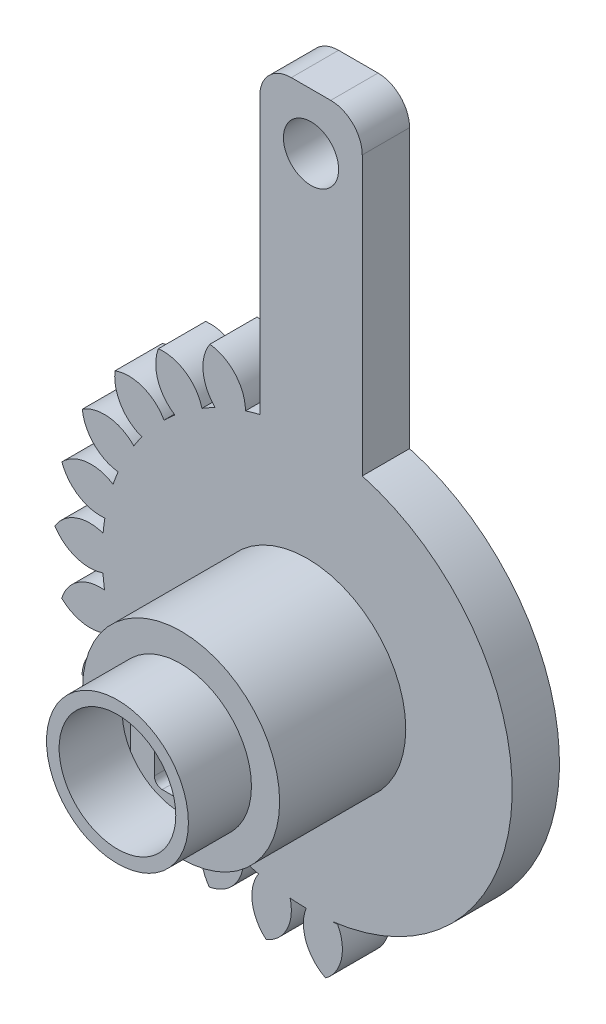
SolidWorks part; units mm, degrees
ref_plane "Front Plane" through (0, 0, 0) normal (0, 0, 1) x (1, 0, 0)
ref_plane "Top Plane" through (0, 0, 0) normal (0, 1, 0) x (1, 0, 0)
ref_plane "Right Plane" through (0, 0, 0) normal (1, 0, 0) x (0, 0, -1)
ref_plane "Plane1" through (0, 0, 5) normal (0, 0, 1) x (1, 0, 0)
ref_plane "Plane2" through (0, 0, 8) normal (0, 0, 1) x (1, 0, 0)
ref_plane "Plane3" through (0, 0, 3) normal (0, 0, 1) x (1, 0, 0)
sketch "Sketch1" plane through (0, 0, 5) normal (0, 0, 1) x (1, 0, 0)
  circle A0 centre (0, 20.9252) radius 4.25
  circle A1 centre (0, 20.9252) radius 5.5
  dimension "D1" = 11
  dimension "D2" = 8.5
sketch "Sketch3" plane through (0, 0, 8) normal (0, 0, 1) x (1, 0, 0)
  line L0 (-3.8726, 20.7752) -> (15.4734, 20.7752) construction
  line L1 (0, 24.8978) -> (0, 8.7425) construction
  line L3 (-1.7, 23.6752) -> (1.7, 23.6752)
  line L4 (-1.7, 23.6752) -> (-1.7, 17.8752)
  line L5 (-1.7, 17.8752) -> (1.7, 17.8752)
  line L6 (1.7, 23.6752) -> (1.7, 17.8752)
  dimension "D1" = 3.4
  dimension "D2" = 5.8
  dimension "D3" = 1.7
  dimension "D4" = 2.9
extrude "Boss-Extrude1" add sketch "Sketch1" along normal blind 9 contours A0
shell "Shell1" thickness 2 removed face at (4.25, 20.9252, 14) outward yes
extrude "Boss-Extrude2" add sketch "Sketch3" along normal blind 6 separate body
shell "Shell2" thickness 1.5 removed face at (0, 20.7752, 14) outward yes
sketch "Sketch7" plane through (0, 0, 3) normal (0, 0, -1) x (-1, 0, 0)
  line L0 (0, 14.6752) -> (0, 35.2199) construction
  line L1 (6.25, 20.9252) -> (-26.894, 20.9252) construction
  circle A0 centre (0, 20.9252) radius 6.25 construction
sketch "Sketch5" plane through (0, 0, 3) normal (0, 0, 1) x (1, 0, 0)
  line L1 (0, 14.6752) -> (0, 35.2199) construction
  line L2 (-6.25, 20.9252) -> (26.894, 20.9252) construction
  circle A0 centre (0, 20.9252) radius 13
extrude "Boss-Extrude3" add sketch "Sketch5" along normal blind 3 contours A0
sketch "Sketch6" plane through (0, 0, 3) normal (0, 0, 1) x (1, 0, 0)
  line L1 (-3.01, 33.0817) -> (3.49, 33.0817)
  line L2 (-3.01, 33.0817) -> (-3.01, 53.0817)
  line L3 (-3.01, 53.0817) -> (3.49, 53.0817)
  line L4 (3.49, 33.0817) -> (3.49, 53.0817)
  dimension "D1" = 20
  dimension "D2" = 6.5
extrude "Boss-Extrude4" add sketch "Sketch6" along normal up to surface (3 mm away) up to face at (6.25, 20.9252, 6)
sketch "Sketch8" plane through (0, 0, 3) normal (0, 0, 1) x (1, 0, 0)
  line L0 (-5.7594, 32.4645) -> (-3.9194, 33.1775)
  line L1 (0.24, 53.0817) -> (0.24, -3.388) construction
  line L2 (3.49, 53.0817) -> (-3.01, 53.0817) construction
  line L3 (13, 20.9252) -> (-7.0281, 20.9252) construction
  line L20 (-8.2588, 30.7699) -> (-6.6328, 31.8881)
  line L21 (-10.3, 28.5446) -> (-8.9758, 30.0076)
  line L22 (-11.7731, 25.9085) -> (-10.8219, 27.6375)
  line L23 (-12.5985, 23.0038) -> (-12.0717, 24.9055)
  line L24 (-12.7318, 19.987) -> (-12.6577, 21.9589)
  line L25 (-12.1657, 17.0208) -> (-12.5485, 18.9567)
  line L26 (-10.9309, 14.2651) -> (-11.7498, 16.0605)
  line L27 (-9.0939, 11.8684) -> (-10.3047, 13.4266)
  line L28 (-6.7536, 9.96) -> (-8.2911, 11.197)
  line L29 (-4.0364, 8.6427) -> (-5.8177, 9.4918)
  line L30 (-1.0886, 7.9876) -> (-3.0177, 8.403)
  line L31 (1.9309, 8.03) -> (-0.042, 7.9892)
  arc A0 (-3.9194, 33.1775) -> (-6.1748, 35.8519) centre (-6.4822, 33.3045) ccw
  arc A3 (-6.1748, 35.8519) -> (-5.7594, 32.4645) centre (-4.0035, 34.399) ccw
  arc A4 (-3.01, 33.572) -> (3.49, 33.448) centre (0, 20.9252) ccw construction
  arc A53 (-6.6328, 31.8881) -> (-9.4442, 33.9702) centre (-9.1558, 31.4205) ccw
  arc A54 (-9.4442, 33.9702) -> (-8.2588, 30.7699) centre (-6.9964, 33.0572) ccw
  arc A55 (-8.9758, 30.0076) -> (-12.1916, 31.3853) centre (-11.323, 28.9708) ccw
  arc A56 (-12.1916, 31.3853) -> (-10.3, 28.5446) centre (-9.5992, 31.0614) ccw
  arc A57 (-10.8219, 27.6375) -> (-14.2687, 28.2364) centre (-12.8667, 26.0873) ccw
  arc A58 (-14.2687, 28.2364) -> (-11.7731, 25.9085) centre (-11.6715, 28.5191) ccw
  arc A59 (-12.0717, 24.9055) -> (-15.5637, 24.6934) centre (-13.7039, 22.9256) ccw
  arc A60 (-15.5637, 24.6934) -> (-12.5985, 23.0038) centre (-13.1017, 25.5674) ccw
  arc A61 (-12.6577, 21.9589) -> (-16.0067, 20.9472) centre (-13.7893, 19.656) ccw
  arc A62 (-16.0067, 20.9472) -> (-12.7318, 19.987) centre (-13.8126, 22.3655) ccw
  arc A63 (-12.5485, 18.9567) -> (-15.5739, 17.1999) centre (-13.1185, 16.4548) ccw
  arc A64 (-15.5739, 17.1999) -> (-12.1657, 17.0208) centre (-13.766, 19.0859) ccw
  arc A65 (-11.7498, 16.0605) -> (-14.2885, 13.6534) centre (-11.7274, 13.4946) ccw
  arc A66 (-14.2885, 13.6534) -> (-10.9309, 14.2651) centre (-12.9643, 15.9055) ccw
  arc A67 (-10.3047, 13.4266) -> (-12.2199, 10.4989) centre (-9.6912, 10.9351) ccw
  arc A68 (-12.2199, 10.4989) -> (-9.0939, 11.8684) centre (-11.4507, 12.9957) ccw
  arc A69 (-8.2911, 11.197) -> (-9.4795, 7.9065) centre (-7.1197, 8.9141) ccw
  arc A70 (-9.4795, 7.9065) -> (-6.7536, 9.96) centre (-9.3069, 10.5134) ccw
  arc A71 (-5.8177, 9.4918) -> (-6.2152, 6.016) centre (-4.1513, 7.5406) ccw
  arc A72 (-6.2152, 6.016) -> (-4.0364, 8.6427) centre (-6.6484, 8.5924) ccw
  arc A73 (-3.0177, 8.403) -> (-2.6029, 4.9292) centre (-0.9462, 6.8887) ccw
  arc A74 (-2.6029, 4.9292) -> (-1.0886, 7.9876) centre (-3.6186, 7.3362) ccw
  arc A75 (-0.042, 7.9892) -> (1.1627, 4.7047) centre (2.3228, 6.9935) ccw
  arc A76 (1.1627, 4.7047) -> (1.9309, 8.03) centre (-0.3808, 6.8127) ccw
  point P26 (0.24, 20.9252)
  point P78 (0.24, 20.9252)
  point P153 (0.24, 20.9252)
  dimension "D1" = 13
extrude "Boss-Extrude5" add sketch "Sketch8" along normal up to surface (3 mm away) up to face at (4.25, 20.9252, 6)
sketch "Sketch9" plane through (0, 0, 3) normal (0, 0, -1) x (-1, 0, 0)
  line L0 (-0.24, 53.0817) -> (-0.24, 49.0919) construction
  line L1 (-3.49, 53.0817) -> (3.01, 53.0817) construction
  circle A0 centre (-0.24, 49.5317) radius 1.75
  dimension "D1" = 3.55
extrude "Cut-Extrude1" cut sketch "Sketch9" against normal up to surface (3 mm away) up to face at (4.25, 20.9252, 6)
fillet "Fillet1" radius 2 2 edges at (3.49, 53.0817, 4.5) (-3.01, 53.0817, 4.5)
sketch "Sketch11" plane through (0, 0, 14) normal (0, 0, 1) x (1, 0, 0)
  circle A0 centre (-0.0386, 20.8822) radius 3.7
  circle A1 centre (-0.0386, 20.8822) radius 4.5
  dimension "D1" = 7.4
  dimension "D2" = 9
extrude "Boss-Extrude7" add sketch "Sketch11" along normal blind 4
fillet "Fillet2" radius 0.5 4 edges at (-1.7, 17.8752, 11) (1.7, 17.8752, 11) (-1.7, 23.6752, 11) (1.7, 23.6752, 11)
